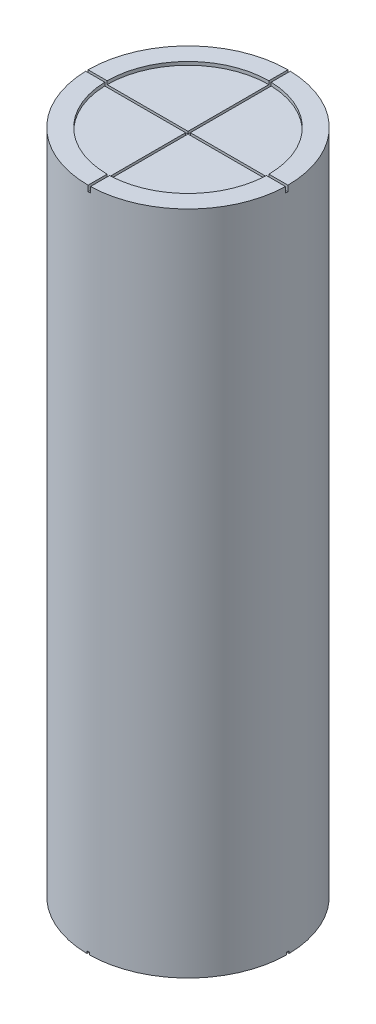
SolidWorks part; units mm, degrees
material "Delrin 2700 NC010, Low Viscosity Acetal Copolymer (SS)"
ref_plane "Front Plane" through (0, 0, 0) normal (0, 0, 1) x (1, 0, 0)
ref_plane "Top Plane" through (0, 0, 0) normal (0, 1, 0) x (1, 0, 0)
ref_plane "Right Plane" through (0, 0, 0) normal (1, 0, 0) x (0, 0, -1)
sketch "Sketch1" plane through (0, 0, 0) normal (0, 1, 0) x (1, 0, 0)
  circle A0 centre (0, 0) radius 10.5
  dimension "D1" = 21
extrude "Boss-Extrude1" add sketch "Sketch1" along normal blind 70
sketch "Sketch2" plane through (0, 70, 0) normal (0, 1, 0) x (1, 0, 0)
  circle A0 centre (0, 0) radius 8.5
  dimension "D1" = 17
extrude "Cut-Extrude1" cut sketch "Sketch2" against normal blind 0.35
sketch "Sketch3" plane through (0, 0, 0) normal (0, 1, 0) x (1, 0, 0)
  line L0 (-10.5, 0) -> (10.5, 0)
  line L1 (0, -10.5) -> (0, 10.5)
  circle A0 centre (0, 0) radius 10.5 construction
  point P5 (0, 0)
  point P11 (0, 0)
extrude "Cut-Extrude-Thin1" cut sketch "Sketch3" along normal blind 0.25 thin thin type mid plane wall 0.25
extrude "Cut-Extrude-Thin2" cut sketch "Sketch3<2>" against normal blind 0.6 from surface thin starting at face at (0, 70, 8.5) thin type one direction wall 0.25
sketch "Sketch3<2>" plane through (0, 0, 0) normal (0, 1, 0) x (1, 0, 0) same geometry as "Sketch3"
